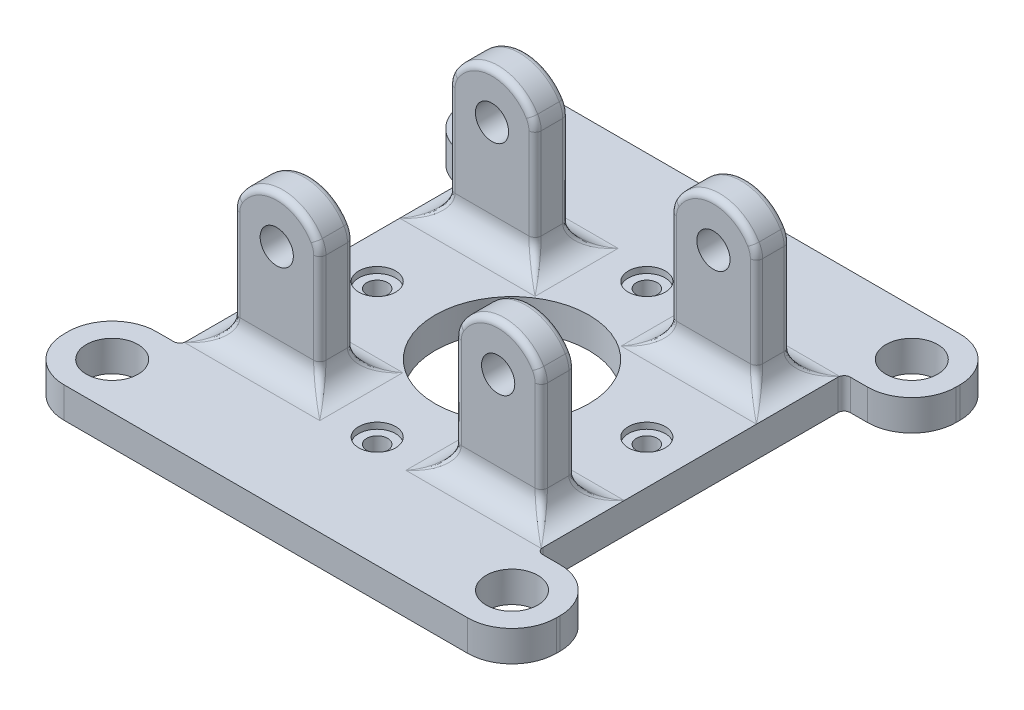
SolidWorks part; units mm, degrees
ref_plane "Front Plane" through (0, 0, 0) normal (0, 0, 1) x (1, 0, 0)
ref_plane "Top Plane" through (0, 0, 0) normal (0, 1, 0) x (1, 0, 0)
ref_plane "Right Plane" through (0, 0, 0) normal (1, 0, 0) x (0, 0, -1)
sketch "Sketch1" plane through (0, 0, 0) normal (0, 1, 0) x (1, 0, 0)
  line L1 (-40, -40) -> (40, -40)
  line L2 (-40, -40) -> (-40, 40)
  line L3 (-40, 40) -> (40, 40)
  line L4 (40, -40) -> (40, 40)
  line L5 (-40, -40) -> (40, 40) construction
  line L6 (-40, 40) -> (40, -40) construction
  circle A0 centre (0, 0) radius 12.5
  point P0 (0, 0)
  dimension "D1" = 25
  dimension "D2" = 80
  dimension "D3" = 80
extrude "Boss-Extrude1 - Base" add sketch "Sketch1" along normal blind 5
sketch "Sketch2" plane through (0, 5, 0) normal (0, 1, 0) x (1, 0, 0)
  line L0 (0, 0) -> (-40, 0) construction
  line L1 (0, 0) -> (0, -40) construction
  line L2 (-40, -40) -> (40, -40) construction
  line L3 (-40, 40) -> (-40, -40) construction
  line L4 (-25, -20.25) -> (-11, -20.25)
  line L5 (-25, 14.75) -> (-11, 14.75)
  line L6 (-25, 14.75) -> (-25, 20.25)
  line L7 (-25, 20.25) -> (-11, 20.25)
  line L8 (-11, 14.75) -> (-11, 20.25)
  line L9 (-25, 14.75) -> (-11, 20.25) construction
  line L10 (-25, 20.25) -> (-11, 14.75) construction
  line L11 (-11, -14.75) -> (-11, -20.25)
  line L12 (-25, -14.75) -> (-11, -14.75)
  line L13 (-25, -14.75) -> (-25, -20.25)
  line L14 (25, -14.75) -> (25, -20.25)
  line L15 (25, -14.75) -> (11, -14.75)
  line L16 (11, -14.75) -> (11, -20.25)
  line L17 (25, -20.25) -> (11, -20.25)
  line L18 (25, 20.25) -> (11, 20.25)
  line L19 (11, 14.75) -> (11, 20.25)
  line L20 (25, 14.75) -> (11, 14.75)
  line L21 (25, 14.75) -> (25, 20.25)
  circle A0 centre (0, 0) radius 5.5 construction
  circle A1 centre (0, 0) radius 12.5 construction
  point P0 (0, 0)
  point P1 (-18, 0)
  point P12 (-18, 17.5)
  point P30 (-5.5, 0)
  dimension "D5" = 11
  dimension "D1" = 12.5
  dimension "D2" = 14.75
  dimension "D3" = 14
  dimension "D4" = 5.5
extrude "Boss-Extrude2 - Flaps" add sketch "Sketch2" along normal blind 25
sketch "Sketch3" plane through (0, 0, 20.25) normal (0, 0, 1) x (1, 0, 0)
  line L0 (-18, 5) -> (-18, 30) construction
  line L1 (-25, 5) -> (-11, 5) construction
  line L2 (-25, 30) -> (-11, 30) construction
  line L3 (-25, 24.6926) -> (-25, 30)
  line L4 (-25, 30) -> (-25, 5) construction
  line L5 (-25, 30) -> (-11, 30)
  line L6 (-11, 30) -> (-11, 5) construction
  line L7 (-11, 30) -> (-11, 24.6926)
  circle A0 centre (-18, 22) radius 2.7
  arc A2 (-11, 24.6926) -> (-25, 24.6926) centre (-18, 22) ccw
  dimension "D1" = 5.4
  dimension "D3" = 7.5
  dimension "D2" = 17
extrude "Cut-Extrude1 - SB hole and flap geo." cut sketch "Sketch3" against normal up to surface (40.5 mm away) up to face at (-18, 17.5, -20.25)
mirror "Mirror1" about plane through (0, 0, 0) normal (1, 0, 0) of "Cut-Extrude1 - SB hole and flap geo."
sketch "Sketch - Screw locations" plane through (0, 5, 0) normal (0, 1, 0) x (1, 0, 0)
  line L0 (0, 0) -> (-40, 0) construction
  line L1 (-40, 40) -> (-40, -40) construction
  line L2 (-40, 0) -> (0, 0) construction
  line L3 (0, 0) -> (0, 40) construction
  line L4 (40, 40) -> (-40, 40) construction
  line L5 (-21.9203, 0) -> (0, 21.9203) construction
  line L12 (-32.5, 32.5) -> (32.5, 32.5) construction
  line L13 (-32.5, 32.5) -> (-32.5, -32.5) construction
  line L14 (-32.5, -32.5) -> (32.5, -32.5) construction
  line L15 (32.5, 32.5) -> (32.5, -32.5) construction
  line L16 (-32.5, 32.5) -> (32.5, -32.5) construction
  line L17 (-32.5, -32.5) -> (32.5, 32.5) construction
  line L18 (0, 21.9203) -> (21.9203, 0) construction
  line L19 (21.9203, 0) -> (0, -21.9203) construction
  line L20 (0, -21.9203) -> (-21.9203, 0) construction
  point P27 (-15, -32.5)
  point P28 (15, -32.5)
  point P29 (-15, 32.5)
  point P30 (15, 32.5)
  dimension "D1" = 32.5
  dimension "D2" = 15
  dimension "D3" = 45
  dimension "D4" = 45
  dimension "D5" = 65
  dimension "D6" = 65
  dimension "D7" = 31
hole_wizard "Ø8.0mm Dowel Hole1" positions "Sketch11" profile "Sketch12" hole size "Ø8.0" standard "ANSI Metric" end condition up to next
sketch "Sketch11" plane through (0, 5, 0) normal (0, 1, 0) x (1, 0, 0)
  point P0 (-32.5, 32.5)
  point P3 (32.5, 32.5)
  point P6 (32.5, -32.5)
  point P9 (-32.5, -32.5)
sketch "Sketch12" plane through (-32.5, 5, -32.5) normal (1, 0, 0) x (0, 0, 1)
  line L0 (0, 0) -> (0, 5)
  line L1 (0, 5) -> (4.2, 5)
  line L2 (4.2, 5) -> (4.2, 0)
  line L5 (4.2, 0) -> (0, 0)
  line L11 (0, -6.35) -> (0, 107.95) construction
  dimension "Thru Hole Dia." = 8.4
  dimension "Thru Hole Depth" = 5
sketch "Sketch13" plane through (0, 5, 0) normal (0, 1, 0) x (1, 0, 0)
  line L0 (0, 0) -> (0, 40) construction
  line L7 (40, 40) -> (-40, 40) construction
  line L8 (0, 40) -> (0, 0) construction
  line L9 (0, 0) -> (-40, 0) construction
  line L10 (-40, 40) -> (-40, -40) construction
  circle A0 centre (-32.5, 32.5) radius 4.1
  circle A8 centre (-32.5, 32.5) radius 6
  circle A9 centre (32.5, 32.5) radius 4.1
  circle A10 centre (32.5, 32.5) radius 6
  circle A11 centre (32.5, -32.5) radius 6
  circle A12 centre (32.5, -32.5) radius 4.1
  circle A13 centre (-32.5, -32.5) radius 6
  circle A14 centre (-32.5, -32.5) radius 4.1
  dimension "D2" = 12
  dimension "D1" = 8.2
extrude "Boss-Extrude3 - Standoff pockets" [suppressed] add sketch "Sketch13" along normal blind 5
ref_axis "Axis1" through (-18, 22, -20.1223) along (0, 0, 1)
ref_plane "Plane1" through (-10.9069, 25.0842, 0) normal (-0.3987, 0.9171, 0) x (0, 0, 1)
hole_wizard "CBORE for M3 Hex Head Machine Screw1" positions "Sketch14" profile "Sketch15" counterbore size "M3" standard "ANSI Metric" end condition through all
sketch "Sketch14" plane through (0, 5, 0) normal (0, 1, 0) x (1, 0, 0)
  point P0 (-21.9203, 0)
  point P3 (0, 21.9203)
  point P6 (21.9203, 0)
  point P9 (0, -21.9203)
sketch "Sketch15" plane through (-21.9203, 5, 0) normal (1, 0, 0) x (0, 0, 1)
  line L0 (0, 0) -> (0, 5)
  line L1 (0, 5) -> (1.7, 5)
  line L3 (1.7, 5) -> (1.7, 1)
  line L4 (1.7, 1) -> (3, 1)
  line L5 (3, 1) -> (3, 0)
  line L7 (3, 0) -> (0, 0)
  line L11 (0, -6.35) -> (0, 107.95) construction
  dimension "Thru Hole Dia." = 3.4
  dimension "Thru Hole Depth" = 5
  dimension "C'Bore Dia." = 6
  dimension "C'Bore Depth" = 1
sketch "Sketch16" plane through (0, 5, 0) normal (0, 1, 0) x (1, 0, 0)
  line L0 (0, 0) -> (0, 7.9921) construction
  line L1 (0, 0) -> (-40, 0) construction
  line L2 (-40, 40) -> (-40, -40) construction
  line L3 (51, 25) -> (29, 25)
  line L4 (-51, -25) -> (-29, -25)
  line L5 (-51, -25) -> (-51, 25)
  line L6 (-51, 25) -> (-29, 25)
  line L7 (-29, -25) -> (-29, 25)
  line L8 (-51, -25) -> (-29, 25) construction
  line L9 (-51, 25) -> (-29, -25) construction
  line L10 (29, -25) -> (29, 25)
  line L11 (51, -25) -> (29, -25)
  line L12 (51, -25) -> (51, 25)
  dimension "D1" = 22
  dimension "D2" = 50
extrude "Cut-Extrude4" cut sketch "Sketch16" against normal up to next
fillet "Fillet1" radius 4 24 edges at (-11, 5, -17.5) (-18, 5, -14.75) (-25, 5, -17.5) (-18, 5, -20.25) (18, 5, -20.25) (11, 5, -17.5) (18, 5, -14.75) (25, 5, -17.5) (25, 5, 17.5) (18, 5, 14.75) (11, 5, 17.5) (18, 5, 20.25) (-11, 5, 17.5) (-18, 5, 14.75) (-25, 5, 17.5) (-18, 5, 20.25) (-25, 24.6926, 17.5) (25, 24.6926, -17.5) (11, 24.6926, -17.5) (-25, 24.6926, -17.5) (-11, 24.6926, -17.5) (25, 24.6926, 17.5) (11, 24.6926, 17.5) (-11, 24.6926, 17.5)
fillet "Fillet2" radius 1 60 edges at (-18, 29.5, 20.25) (-26.1716, 6.1716, 21.4216) (-25, 16.4014, 20.25) (-24.8545, 24.8718, 20.25) (-9.8284, 6.1716, 21.4216) (-11, 16.4014, 20.25) (-11.1455, 24.8718, 20.25) (26.1716, 6.1716, 21.4216) (25, 16.4014, 20.25) (24.8545, 24.8718, 20.25) (18, 29.5, 20.25) (9.8284, 6.1716, 21.4216) (11, 16.4014, 20.25) (9.8284, 6.1716, 13.5784) (11, 16.4014, 14.75) (26.1716, 6.1716, 13.5784) (25, 16.4014, 14.75) (24.8545, 24.8718, 14.75) (18, 29.5, 14.75) (26.1716, 6.1716, -13.5784) (25, 16.4014, -14.75) (24.8545, 24.8718, -14.75) (18, 29.5, -14.75) (9.8284, 6.1716, -13.5784) (11, 16.4014, -14.75) (9.8284, 6.1716, -21.4216) (11, 16.4014, -20.25) (26.1716, 6.1716, -21.4216) (25, 16.4014, -20.25) (24.8545, 24.8718, -20.25) (18, 29.5, -20.25) (-9.8284, 6.1716, -13.5784) (-11, 16.4014, -14.75) (-11.1455, 24.8718, -14.75) (-18, 29.5, -14.75) (-26.1716, 6.1716, -13.5784) (-25, 16.4014, -14.75) (-26.1716, 6.1716, -21.4216) (-25, 16.4014, -20.25) (-9.8284, 6.1716, -21.4216) (-11, 16.4014, -20.25) (-11.1455, 24.8718, -20.25) (-18, 29.5, -20.25) (-26.1716, 6.1716, 13.5784) (-25, 16.4014, 14.75) (-24.8545, 24.8718, 14.75) (-9.8284, 6.1716, 13.5784) (-11, 16.4014, 14.75) (-11.1455, 24.8718, 14.75) (11.1455, 24.8718, 20.25) (11.1455, 24.8718, 14.75) (11.1455, 24.8718, -14.75) (11.1455, 24.8718, -20.25) (-24.8545, 24.8718, -14.75) (-24.8545, 24.8718, -20.25) (-18, 29.5, 14.75) (-29, 2.5, -25) (-29, 2.5, 25) (29, 2.5, -25) (29, 2.5, 25)
fillet "Fillet3" radius 7.2 8 edges at (40, 2.5, 25) (40, 2.5, 40) (40, 2.5, -25) (40, 2.5, -40) (-40, 2.5, 40) (-40, 2.5, 25) (-40, 2.5, -40) (-40, 2.5, -25)
fillet "Fillet4" [suppressed] radius 3
